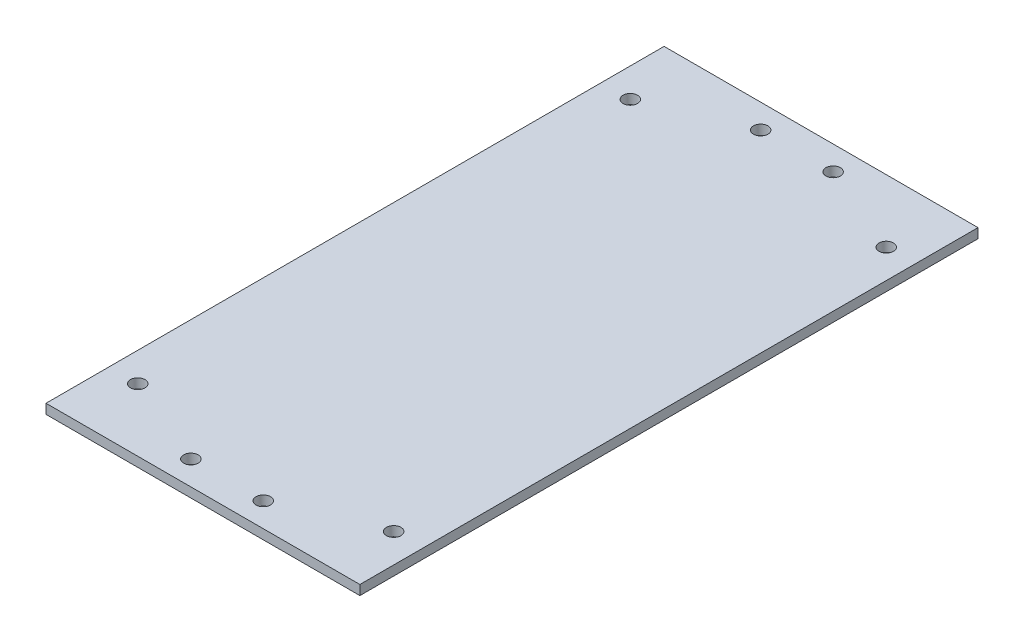
SolidWorks part; units mm, degrees
ref_plane "Спереди" through (0, 0, 0) normal (0, 0, 1) x (1, 0, 0)
ref_plane "Сверху" through (0, 0, 0) normal (0, 1, 0) x (1, 0, 0)
ref_plane "Справа" through (0, 0, 0) normal (1, 0, 0) x (0, 0, -1)
sketch "Эскиз1" plane through (0, 0, 0) normal (0, 1, 0) x (1, 0, 0)
  line L0 (-41.8585, 53.6415) -> (-41.8585, -74.3585) construction
  line L1 (-74.3585, 53.6415) -> (-9.3585, 53.6415)
  line L2 (-74.3585, 53.6415) -> (-74.3585, -74.3585)
  line L3 (-74.3585, -74.3585) -> (-9.3585, -74.3585)
  line L4 (-9.3585, 53.6415) -> (-9.3585, -74.3585)
  line L5 (-74.3585, -10.3585) -> (-9.3585, -10.3585) construction
  circle A0 centre (-68.3585, 40.6415) radius 1.5
  circle A1 centre (-15.3585, 40.6415) radius 1.5
  circle A2 centre (-15.3585, -61.3585) radius 1.5
  circle A3 centre (-68.3585, -61.3585) radius 1.5
  point P0 (0, 0)
  point P12 (-41.8585, -10.3585)
  dimension "D1" = 13
  dimension "D2" = 6
  dimension "D3" = 128
  dimension "D4" = 65
extrude "Бобышка-Вытянуть1" add sketch "Эскиз1" along normal blind 2
sketch "Эскиз2" plane through (0, 2, 0) normal (0, 1, 0) x (1, 0, 0)
  line L0 (-41.8585, 53.6415) -> (-41.8585, -74.3585) construction
  line L1 (-9.3585, 53.6415) -> (-74.3585, 53.6415) construction
  line L2 (-74.3585, -74.3585) -> (-9.3585, -74.3585) construction
  line L3 (-74.3585, -10.3585) -> (-9.3585, -10.3585) construction
  line L4 (-74.3585, 53.6415) -> (-74.3585, -74.3585) construction
  line L5 (-9.3585, -74.3585) -> (-9.3585, 53.6415) construction
  circle A0 centre (-49.3585, 48.6415) radius 1.5
  circle A1 centre (-34.3585, 48.6415) radius 1.5
  circle A2 centre (-34.3585, -69.3585) radius 1.5
  circle A3 centre (-49.3585, -69.3585) radius 1.5
  dimension "D1" = 3
  dimension "D2" = 5
  dimension "D3" = 7.5
extrude "Вырез-Вытянуть1" cut sketch "Эскиз2" against normal through all
